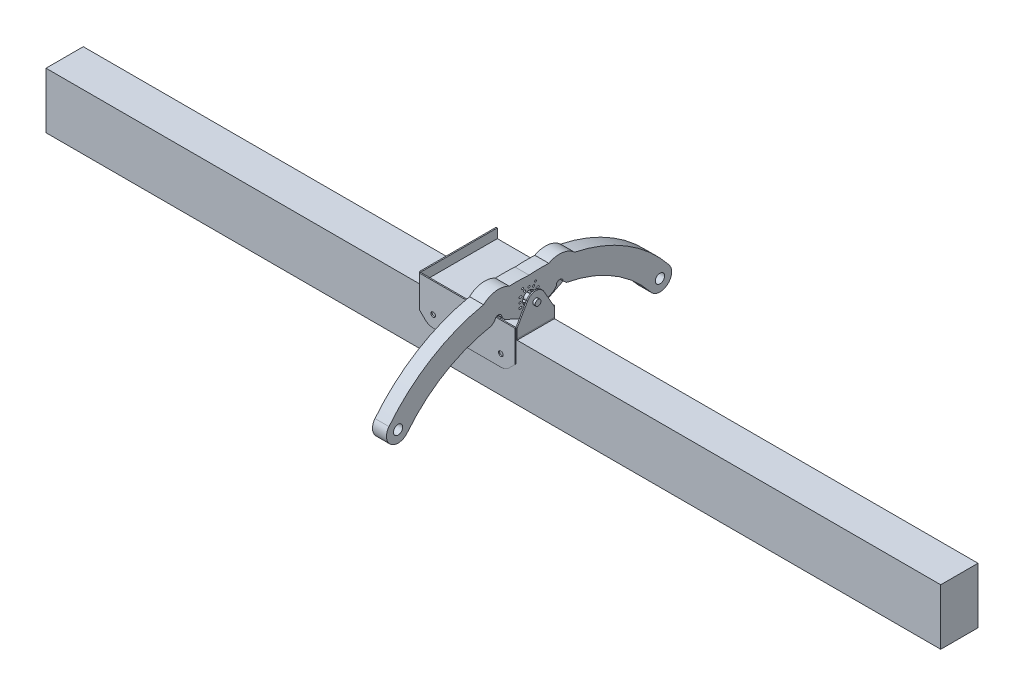
SolidWorks part; units mm, degrees
ref_plane "Front Plane" through (0, 0, 0) normal (0, 0, 1) x (1, 0, 0)
ref_plane "Top Plane" through (0, 0, 0) normal (0, 1, 0) x (1, 0, 0)
ref_plane "Right Plane" through (0, 0, 0) normal (1, 0, 0) x (0, 0, -1)
other "Bounding Box"
ref_plane "Default Plane" through (-8.9266, -12.7485, 0) normal (-0.1736, 0.9848, 0) x (0.9848, 0.1736, 0)
sketch "Sketch1" plane through (0, 0, 0) normal (1, 0, 0) x (0, 0, -1)
  line L0 (26.4895, 47.7116) -> (97.9745, 8.0232)
  line L1 (22.4975, -49.7187) -> (96.9898, -16.0113)
  line L2 (0, 0) -> (91.44, -3.7465) construction
  line L3 (0, -149.6129) -> (0, 49850.3871) construction
  line L4 (62.94, 24.7535) -> (119.94, 24.7535)
  line L5 (62.94, 24.7535) -> (62.94, -32.2465)
  line L6 (62.94, -32.2465) -> (119.94, -32.2465)
  line L7 (119.94, 24.7535) -> (119.94, -32.2465)
  line L8 (62.94, 24.7535) -> (119.94, -32.2465) construction
  line L9 (62.94, -32.2465) -> (119.94, 24.7535) construction
  line L10 (-50.8, -218.44) -> (50.8, -218.44)
  line L11 (-50.8, -218.44) -> (-50.8, -66.04)
  line L12 (-50.8, -66.04) -> (50.8, -66.04)
  line L13 (50.8, -218.44) -> (50.8, -66.04)
  line L14 (-50.8, -218.44) -> (50.8, -66.04) construction
  line L15 (-50.8, -66.04) -> (50.8, -218.44) construction
  line L16 (40.64, -3.7465) -> (40.64, -58.1025)
  line L17 (40.64, -58.1025) -> (142.24, -58.1025)
  line L18 (142.24, -58.1025) -> (142.24, -3.7465)
  line L19 (-33.0655, -62.865) -> (49966.9345, -62.865) construction
  line L20 (-356.8721, -133.429) -> (0, 0) construction
  line L21 (0, 0) -> (356.8721, -133.429) construction
  line L22 (-356.8721, -133.429) -> (356.8721, -133.429) construction
  arc A0 (26.4895, 47.7116) -> (22.4975, -49.7187) centre (0, 0) ccw
  arc A1 (96.9898, -16.0113) -> (97.9745, 8.0232) centre (91.44, -3.7465) ccw
  circle A2 centre (91.44, -3.7465) radius 50.8
  circle A3 centre (0, 0) radius 58.6105 construction
  circle A4 centre (0, 0) radius 7.9375
  circle A5 centre (0, 0) radius 17.4625
  point P13 (0, -142.24)
  point P29 (58.6105, 0)
  point P31 (7.9375, 0)
  point P32 (17.4625, 0)
  point P33 (0, -66.04)
  point P34 (0, -62.865)
  line B0 (-25.4, 10.2108) -> (-21.997, 10.2108)
  line B1 (-10.3326, -22.766) -> (-9.8529, -21.2892)
  line B2 (-13.5106, -19.1774) -> (-14.5497, -20.3313)
  line B3 (24.8822, 2.4348) -> (23.3634, 2.1118)
  line B4 (23.3634, -2.1118) -> (24.8822, -2.4348)
  line B5 (21.997, -15.1892) -> (25.4, -15.1892)
  line B6 (25.4, -10.2108) -> (21.997, -10.2108)
  line B7 (14.5497, -20.3313) -> (13.5106, -19.1774)
  line B8 (9.8529, -21.2892) -> (10.3326, -22.766)
  circle B9 centre (0, 0) radius 57.2931
  arc B10 (2.4892, 25.4) -> (-2.4892, 25.4) centre (0, 25.4) ccw
  arc B11 (19.9517, 30.1625) -> (14.9733, 30.1625) centre (17.4625, 30.1625) ccw
  arc B12 (-21.997, 10.2108) -> (-19.5078, 12.7) centre (-21.997, 12.7) ccw
  arc B13 (-14.9733, -30.1625) -> (-19.9517, -30.1625) centre (-17.4625, -30.1625) ccw
  arc B14 (-19.9517, -30.1625) -> (-14.9733, -30.1625) centre (-17.4625, -30.1625) ccw
  arc B15 (-14.9733, 30.1625) -> (-19.9517, 30.1625) centre (-17.4625, 30.1625) ccw
  arc B16 (2.0452, 14.1404) -> (-2.0452, 14.1404) centre (0, 0) ccw
  arc B17 (2.0452, 14.1404) -> (3.667, 14.6219) centre (2.3342, 16.1389) ccw
  arc B18 (13.2685, 5.299) -> (11.2233, 8.8414) centre (0, 0) ccw
  arc B19 (14.4964, -4.1352) -> (14.4964, 4.1352) centre (13.0969, 0) ccw
  arc B20 (11.2233, -8.8414) -> (13.2685, -5.299) centre (0, 0) ccw
  arc B21 (3.667, -14.6219) -> (10.8294, -10.4867) centre (6.5484, -11.3422) ccw
  arc B22 (-2.0452, -14.1404) -> (-3.667, -14.6219) centre (-2.3342, -16.1389) ccw
  arc B23 (-10.8294, -10.4867) -> (-11.2233, -8.8414) centre (-12.8096, -10.0909) ccw
  arc B24 (-11.2233, 8.8414) -> (-13.2685, 5.299) centre (0, 0) ccw
  arc B25 (-3.667, 14.6219) -> (-10.9141, 11.3422) centre (-6.5484, 11.3422) ccw
  arc B26 (-14.5497, -20.3313) -> (-10.3326, -22.766) centre (-12.7, -21.997) ccw
  arc B27 (-24.8822, 2.4348) -> (-24.8822, -2.4348) centre (-25.4, 0) ccw
  arc B28 (-10.3326, 22.766) -> (-14.5497, 20.3313) centre (-12.7, 21.997) ccw
  arc B29 (14.9733, -30.1625) -> (19.9517, -30.1625) centre (17.4625, -30.1625) ccw
  arc B30 (19.9517, -30.1625) -> (14.9733, -30.1625) centre (17.4625, -30.1625) ccw
  arc B31 (27.8892, 0) -> (24.8822, 2.4348) centre (25.4, 0) ccw
  arc B32 (24.8822, -2.4348) -> (27.8892, 0) centre (25.4, 0) ccw
  arc B33 (23.3634, 2.1118) -> (23.3634, -2.1118) centre (23.8125, 0) ccw
  arc B34 (21.997, 15.1892) -> (21.997, 10.2108) centre (21.997, 12.7) ccw
  arc B35 (27.8892, -12.7) -> (25.4, -10.2108) centre (25.4, -12.7) ccw
  arc B36 (25.4, -15.1892) -> (27.8892, -12.7) centre (25.4, -12.7) ccw
  arc B37 (21.997, -10.2108) -> (21.997, -15.1892) centre (21.997, -12.7) ccw
  arc B38 (15.1892, -21.997) -> (14.5497, -20.3313) centre (12.7, -21.997) ccw
  arc B39 (10.3326, -22.766) -> (15.1892, -21.997) centre (12.7, -21.997) ccw
  arc B40 (13.5106, -19.1774) -> (9.8529, -21.2892) centre (11.9063, -20.6222) ccw
  arc B41 (9.8529, 21.2892) -> (13.5106, 19.1774) centre (11.9062, 20.6222) ccw
  arc B42 (-2.4892, -25.4) -> (2.4892, -25.4) centre (0, -25.4) ccw
  arc B43 (2.4892, -25.4) -> (-2.4892, -25.4) centre (0, -25.4) ccw
  dimension "D1" = 13.462
  dimension "D2" = 117.221
  dimension "D4" = 101.6
  dimension "D11" = 54.5719
  dimension "D13" = 15.875
  dimension "D14" = 34.925
  dimension "D3" = 57
  dimension "D5" = 152.4
  dimension "D6" = 101.6
  dimension "D7" = 66.04
  dimension "D8" = 54.356
  dimension "D9" = 3.175
  dimension "D10" = 4.7625
  dimension "D12" = 91.44
  dimension "D15" = 139
  dimension "D16" = 381
sketch_block_instance "Block-WCP 36T Sprocket Block-1"
sketch_block "Block-WCP 36T Sprocket Block"
sketch "Sketch2" plane through (0, 0, 0) normal (0, 1, 0) x (1, 0, 0)
  line L0 (-185.2438, 91.44) -> (49814.7562, 91.44) construction
  line L1 (-1.9939, 58.6105) -> (1.9939, 58.6105)
  line L2 (-1.9939, 58.6105) -> (-1.9939, -58.6105)
  line L3 (-1.9939, -58.6105) -> (1.9939, -58.6105)
  line L4 (1.9939, 58.6105) -> (1.9939, -58.6105)
  line L5 (-1.9939, 58.6105) -> (1.9939, -58.6105) construction
  line L6 (-1.9939, -58.6105) -> (1.9939, 58.6105) construction
  line L7 (-88.9, 119.94) -> (-17.78, 119.94)
  line L8 (-88.9, 119.94) -> (-88.9, 62.94)
  line L9 (-88.9, 62.94) -> (-17.78, 62.94)
  line L10 (-17.78, 119.94) -> (-17.78, 62.94)
  line L11 (-88.9, 119.94) -> (-17.78, 62.94) construction
  line L12 (-88.9, 62.94) -> (-17.78, 119.94) construction
  line L13 (-180.975, 142.24) -> (-92.075, 142.24)
  line L14 (-180.975, 142.24) -> (-180.975, 40.64)
  line L15 (-180.975, 40.64) -> (-92.075, 40.64)
  line L16 (-92.075, 142.24) -> (-92.075, 40.64)
  line L17 (-180.975, 142.24) -> (-92.075, 40.64) construction
  line L18 (-180.975, 40.64) -> (-92.075, 142.24) construction
  line L19 (0, -356.8721) -> (0, 356.8721) construction
  line L20 (0, 0) -> (50000, 0) construction
  line L21 (-17.78, 62.94) -> (-17.78, -49937.06) construction
  line L22 (71.12, 7.9375) -> (-24.13, 7.9375)
  line L23 (71.12, 7.9375) -> (71.12, -7.9375)
  line L24 (71.12, -7.9375) -> (-24.13, -7.9375)
  line L25 (-24.13, 7.9375) -> (-24.13, -7.9375)
  line L26 (71.12, 7.9375) -> (-24.13, -7.9375) construction
  line L27 (71.12, -7.9375) -> (-24.13, 7.9375) construction
  line L28 (8.3439, 356.8721) -> (46.4439, 356.8721)
  line L29 (8.3439, 356.8721) -> (8.3439, -356.8721)
  line L30 (8.3439, -356.8721) -> (46.4439, -356.8721)
  line L31 (46.4439, 356.8721) -> (46.4439, -356.8721)
  line L32 (8.3439, 356.8721) -> (46.4439, -356.8721) construction
  line L33 (8.3439, -356.8721) -> (46.4439, 356.8721) construction
  line L34 (-14.605, 51.574) -> (-14.605, -49948.426) construction
  line L35 (61.595, -32.0782) -> (61.595, 49967.9218) construction
  line L36 (-3.4925, 16.6624) -> (-14.605, 16.6624)
  line L37 (-3.4925, 16.6624) -> (-3.4925, -16.6624)
  line L38 (-3.4925, -16.6624) -> (-14.605, -16.6624)
  line L39 (-14.605, 16.6624) -> (-14.605, -16.6624)
  line L40 (-3.4925, 16.6624) -> (-14.605, -16.6624) construction
  line L41 (-3.4925, -16.6624) -> (-14.605, 16.6624) construction
  line L42 (-1.9939, 17.4625) -> (6.7437, 17.4625)
  line L43 (-1.9939, 17.4625) -> (-1.9939, -17.4625)
  line L44 (-1.9939, -17.4625) -> (6.7437, -17.4625)
  line L45 (6.7437, 17.4625) -> (6.7437, -17.4625)
  line L46 (-1.9939, 17.4625) -> (6.7437, -17.4625) construction
  line L47 (-1.9939, -17.4625) -> (6.7437, 17.4625) construction
  line L48 (37.7063, 17.4625) -> (46.4439, 17.4625)
  line L49 (37.7063, 17.4625) -> (37.7063, -17.4625)
  line L50 (37.7063, -17.4625) -> (46.4439, -17.4625)
  line L51 (46.4439, 17.4625) -> (46.4439, -17.4625)
  line L52 (37.7063, 17.4625) -> (46.4439, -17.4625) construction
  line L53 (37.7063, -17.4625) -> (46.4439, 17.4625) construction
  line L58 (-68.8345, 50.8) -> (49931.1655, 50.8)
  line L59 (-72.6975, -50.8) -> (49927.3025, -50.8)
  line L60 (64.77, 18.8635) -> (64.77, -49981.1365) construction
  line L62 (50.4825, 16.6624) -> (61.595, 16.6624)
  line L63 (50.4825, 16.6624) -> (50.4825, -16.6624)
  line L64 (50.4825, -16.6624) -> (61.595, -16.6624)
  line L65 (61.595, 16.6624) -> (61.595, -16.6624)
  line L66 (50.4825, 16.6624) -> (61.595, -16.6624) construction
  line L67 (50.4825, -16.6624) -> (61.595, 16.6624) construction
  point P0 (0, 0)
  point P6 (-53.34, 91.44)
  point P12 (-136.525, 91.44)
  point P19 (23.495, 0)
  point P31 (27.3939, 0)
  point P42 (-9.0487, 0)
  point P47 (2.3749, 0)
  point P52 (42.0751, 0)
  point P65 (56.0388, 0)
  point P71 (64.77, 0)
  point P72 (61.595, 0)
  point P73 (-17.78, 0)
  point P74 (64.77, -50.8)
  dimension "D1" = 3.9878
  dimension "D2" = 3.175
  dimension "D3" = 71.12
  dimension "D4" = 88.9
  dimension "D5" = 17.78
  dimension "D6" = 38.1
  dimension "D7" = 6.35
  dimension "D8" = 3.175
  dimension "D9" = 33.3248
  dimension "D10" = 11.1125
  dimension "D11" = 6.35
  dimension "D12" = 8.7376
  dimension "D13" = 76.2
  dimension "D14" = 3.175
  dimension "D15" = 6.35
sketch "Sketch3" plane through (0, 0, 0) normal (1, 0, 0) x (0, 0, -1)
  line L0 (-50.8, -218.44) -> (50.8, -218.44)
  line L1 (50.8, -218.44) -> (50.8, -66.04)
  line L2 (50.8, -66.04) -> (-50.8, -66.04)
  line L3 (-50.8, -66.04) -> (-50.8, -218.44)
extrude "Boss-Extrude1" add sketch "Sketch3" along normal mid plane 2438.4
sketch "Sketch11" plane through (0, -66.04, 0) normal (0, 1, 0) x (1, 0, 0)
  line L0 (-198.755, -50.8) -> (64.77, -50.8)
  line L1 (64.77, -50.8) -> (64.77, 50.8)
  line L2 (-200068.8345, 50.8) -> (249931.1655, 50.8) construction
  line L4 (-14.605, 200051.574) -> (-14.605, -249948.426) construction
  line L5 (-17.78, 158.75) -> (-198.755, 158.75)
  line L6 (-198.755, 158.75) -> (-198.755, -50.8)
  line L7 (64.77, 200018.8635) -> (64.77, -249981.1365) construction
  line L8 (-200072.6975, -50.8) -> (249927.3025, -50.8) construction
  line L9 (-17.78, 200062.94) -> (-17.78, -249937.06) construction
  line L10 (-17.78, 158.75) -> (-17.78, 50.8)
  line L11 (-17.78, 50.8) -> (64.77, 50.8)
  dimension "D1" = 184.15
  dimension "D2" = 107.95
extrude "Boss-Extrude5" add sketch "Sketch11" along normal up to vertex (3.175 mm away) separate body up to point (0, -62.865, 0)
sketch "Sketch12" plane through (0, 0, 0) normal (1, 0, 0) x (0, 0, -1)
  line L0 (-50.8, -62.865) -> (50.8, -62.865)
  line L3 (-50.8, -62.865) -> (-50.8, -37.465)
  line L4 (-50.8, -37.465) -> (-22.0274, 12.6473)
  line L5 (50.8, -62.865) -> (50.8, -37.465)
  line L6 (50.8, -37.465) -> (22.0274, 12.6473)
  line L7 (-50.8, -62.865) -> (50.8, -62.865) construction
  arc A0 (-22.0274, 12.6473) -> (22.0274, 12.6473) centre (0, 0) cw
  circle A1 centre (0, 0) radius 7.9375 construction
  circle A2 centre (0, 0) radius 7.9375
  dimension "D2" = 25.4
  dimension "D1" = 25.4
extrude "Boss-Extrude6" add sketch "Sketch12" along normal up to vertex (64.77 mm away) from vertex separate body up to point (64.77, 0, 50.8) starting at point (61.595, 0, 16.6624)
sketch "Sketch13" plane through (0, 0, 50.8) normal (0, 0, 1) x (1, 0, 0)
  line L0 (-198.755, -66.04) -> (-198.755, -123.6413)
  line L1 (-198.755, -123.6413) -> (-183.1056, -139.2906)
  line L2 (61.595, -66.04) -> (61.595, -123.6413)
  line L3 (61.595, -123.6413) -> (45.9456, -139.2906)
  line L4 (-160.655, -148.59) -> (23.495, -148.59)
  line L5 (-160.655, -116.84) -> (-68.58, -116.84) construction
  line L6 (-68.58, -116.84) -> (23.495, -116.84) construction
  line L7 (1219.2, -66.04) -> (-1219.2, -66.04) construction
  line L8 (-198.755, -66.04) -> (61.595, -66.04)
  line L9 (61.595, -37.465) -> (61.595, -62.865) construction
  line L11 (-198.755, -62.865) -> (-198.755, -66.04) construction
  arc A0 (-183.1056, -139.2906) -> (-160.655, -148.59) centre (-160.655, -116.84) ccw
  arc A1 (45.9456, -139.2906) -> (23.495, -148.59) centre (23.495, -116.84) cw
  circle A2 centre (-160.655, -116.84) radius 6.35
  circle A3 centre (23.495, -116.84) radius 6.35
  circle A4 centre (-68.58, -116.84) radius 6.35
  point P18 (64.77, -66.04)
  point P19 (64.77, -66.04)
  point P24 (-194.0557, -66.04)
  dimension "D1" = 12.7
  dimension "D3" = 31.75
  dimension "D2" = 38.1
  dimension "D4" = 50.8
  dimension "D5" = 45
extrude "Boss-Extrude7" add sketch "Sketch13" along normal blind 3.175 separate body
extrude "Boss-Extrude8" add sketch "Sketch13<2>" against normal blind 3.175 from vertex separate body starting at point (0, -218.44, -50.8)
sketch "Sketch13<2>" plane through (0, 0, 50.8) normal (0, 0, 1) x (1, 0, 0) same geometry as "Sketch13"
sketch "Sketch14" plane through (0, 0, 0) normal (1, 0, 0) x (0, 0, -1)
  line L0 (-50.8, -62.865) -> (158.75, -62.865)
  line L1 (-200033.0655, -62.865) -> (249966.9345, -62.865) construction
  line L2 (158.75, -62.865) -> (158.75, -37.465)
  line L3 (158.75, -37.465) -> (119.3185, -7.0377)
  line L4 (-50.8, -62.865) -> (-50.8, -37.465)
  line L5 (-50.8, -37.465) -> (-21.997, 12.7)
  line L6 (11.2488, 22.7733) -> (70.253, -6.3717)
  line L8 (67.4408, -12.065) -> (115.4392, -12.065) construction
  arc A0 (-21.997, 12.7) -> (11.2488, 22.7733) centre (0, 0) cw
  arc A1 (73.4406, -9.9854) -> (109.4394, -9.9854) centre (91.44, -3.7465) ccw
  arc A2 (119.3185, -7.0377) -> (109.4394, -9.9854) centre (115.4392, -12.065) ccw
  arc A3 (70.253, -6.3717) -> (73.4406, -9.9854) centre (67.4408, -12.065) cw
  circle A4 centre (0, 0) radius 7.9375 construction
  circle A5 centre (0, 0) radius 7.9375
  point P23 (161.1346, -62.865)
  point P24 (158.75, -62.865)
  point P25 (158.75, -62.865)
  point P29 (115.4392, -5.715)
  dimension "D1" = 19.05
  dimension "D4" = 6.35
  dimension "D3" = 57.15
extrude "Boss-Extrude9" add sketch "Sketch14" along normal up to vertex (-14.605 mm away) from vertex separate body up to point (-14.605, 0, -16.6624) starting at point (-17.78, 0, 0)
sketch "Sketch4" plane through (0, 0, 0) normal (1, 0, 0) x (0, 0, -1)
  line L0 (0, -44.45) -> (0, 53.0661)
  line L2 (-102.3094, -15.3884) -> (-82.8518, 0.9384)
  line L3 (-82.8518, 0.9384) -> (-66.525, -18.5191)
  line L4 (0, -200149.6129) -> (0, 249850.3871) construction
  line L6 (-66.525, -18.5191) -> (-18.4414, -40.444)
  line L7 (-53.975, -88.265) -> (-53.975, -62.865) construction
  line L9 (-53.975, -62.865) -> (-28.575, -62.865) construction
  line L11 (-66.525, -18.5191) -> (0, 0) construction
  line L12 (0, 0) -> (-28.575, -62.865) construction
  line L13 (-102.3094, -15.3884) -> (-66.525, -18.5191) construction
  line L14 (-53.975, -88.265) -> (-28.575, -62.865) construction
  line L15 (-53.975, -88.265) -> (0, 0) construction
  line L16 (0, 0) -> (-102.3094, -15.3884) construction
  line L17 (-53.975, -123.6413) -> (-53.975, -66.04) construction
  line L18 (-200033.0655, -62.865) -> (249966.9345, -62.865) construction
  circle A0 centre (-356.8721, -133.429) radius 12.7
  arc A2 (-332.0111, -153.1773) -> (-381.7331, -113.6808) centre (-356.8721, -133.429) cw
  arc A3 (-18.4414, -40.444) -> (0, -44.45) centre (0, 0) ccw
  arc A4 (-332.0111, -153.1773) -> (-102.3094, -15.3884) centre (-33.6791, -390.1562) cw
  arc A5 (-381.7331, -113.6808) -> (-123.9731, 45.0762) centre (-33.6791, -390.1562) cw
  arc A6 (-53.9367, 53.882) -> (0, 53.0661) centre (-33.6791, -390.1562) cw
  arc A7 (-123.9731, 45.0762) -> (-53.9367, 53.882) centre (-82.8518, 0.9384) cw
  point P19 (-57.0317, -60.6593)
  point P25 (-54.1049, 49.2027)
  point P26 (-66.3818, 49.8029)
  dimension "D1" = 19.05
  dimension "D2" = 25.4
  dimension "D3" = 44.45
  dimension "D7" = 381
  dimension "D8" = 60.325
  dimension "D4" = 25.4
  dimension "D5" = 25.4
  dimension "D6" = 50
extrude "Boss-Extrude2" add sketch "Sketch4" along normal up to vertex (46.4439 mm away) from vertex separate body up to point (46.4439, 0, 356.8721) starting at point (8.3439, 0, 356.8721)
sketch "Sketch5" plane through (46.4439, 0, 0) normal (1, 0, 0) x (0, 0, -1)
  line L0 (-88.0113, -3.3909) -> (-83.682, -8.5503) construction
  line L1 (-102.3094, -15.3884) -> (-82.8518, 0.9384) construction
  line L2 (-83.682, -8.5503) -> (-78.5225, -4.2211) construction
  line L3 (-82.8518, 0.9384) -> (-66.525, -18.5191) construction
  circle A0 centre (-83.682, -8.5503) radius 9.525
  dimension "D1" = 19.05
extrude "Cut-Extrude1" cut sketch "Sketch5" against normal through all
mirror "Mirror1" about plane through (0, 0, 0) normal (0, 0, 1) of bodies 106
sketch "Sketch6" plane through (8.3439, 0, 0) normal (-1, 0, 0) x (0, 0, 1)
  circle A0 centre (0, 0) radius 44.45
  arc A1 (-18.4414, -40.444) -> (18.4414, -40.444) centre (0, 0) ccw construction
extrude "Boss-Extrude3" add sketch "Sketch6" along normal up to vertex (6.35 mm away) separate body up to point (1.9939, 0, 58.6105)
sketch "Sketch7" plane through (1.9939, 0, 0) normal (-1, 0, 0) x (0, 0, 1)
  line L0 (-24.8822, 2.4348) -> (-23.3634, 2.1118) construction
  line L1 (-23.3634, -2.1118) -> (-24.8822, -2.4348) construction
  line L2 (-25.4, -10.2108) -> (-21.997, -10.2108) construction
  line L3 (-21.997, -15.1892) -> (-25.4, -15.1892) construction
  line L4 (-9.8529, -21.2892) -> (-10.3326, -22.766) construction
  line L5 (-14.5497, -20.3313) -> (-13.5106, -19.1774) construction
  line L6 (-24.8822, 2.4348) -> (-23.3634, 2.1118)
  line L7 (-23.3634, -2.1118) -> (-24.8822, -2.4348)
  line L8 (-25.4, -10.2108) -> (-21.997, -10.2108)
  line L9 (-21.997, -15.1892) -> (-25.4, -15.1892)
  line L10 (-9.8529, -21.2892) -> (-10.3326, -22.766)
  line L11 (-14.5497, -20.3313) -> (-13.5106, -19.1774)
  arc A0 (-27.8892, 0) -> (-24.8822, -2.4348) centre (-25.4, 0) ccw construction
  arc A1 (-24.8822, 2.4348) -> (-27.8892, 0) centre (-25.4, 0) ccw construction
  arc A2 (-23.3634, -2.1118) -> (-23.3634, 2.1118) centre (-23.8125, 0) ccw construction
  arc A3 (-25.4, -10.2108) -> (-27.8892, -12.7) centre (-25.4, -12.7) ccw construction
  arc A4 (-27.8892, -12.7) -> (-25.4, -15.1892) centre (-25.4, -12.7) ccw construction
  arc A5 (-21.997, -15.1892) -> (-21.997, -10.2108) centre (-21.997, -12.7) ccw construction
  arc A6 (-2.4892, -25.4) -> (2.4892, -25.4) centre (0, -25.4) ccw construction
  arc A7 (2.4892, -25.4) -> (-2.4892, -25.4) centre (0, -25.4) ccw construction
  arc A8 (-9.8529, -21.2892) -> (-13.5106, -19.1774) centre (-11.9063, -20.6222) ccw construction
  arc A9 (-14.5497, -20.3313) -> (-15.1892, -21.997) centre (-12.7, -21.997) ccw construction
  arc A10 (-15.1892, -21.997) -> (-10.3326, -22.766) centre (-12.7, -21.997) ccw construction
  arc A11 (-14.9733, -30.1625) -> (-19.9517, -30.1625) centre (-17.4625, -30.1625) ccw construction
  arc A12 (-19.9517, -30.1625) -> (-14.9733, -30.1625) centre (-17.4625, -30.1625) ccw construction
  arc A13 (-27.8892, 0) -> (-24.8822, -2.4348) centre (-25.4, 0) ccw
  arc A14 (-24.8822, 2.4348) -> (-27.8892, 0) centre (-25.4, 0) ccw
  arc A15 (-23.3634, -2.1118) -> (-23.3634, 2.1118) centre (-23.8125, 0) ccw
  arc A16 (-25.4, -10.2108) -> (-27.8892, -12.7) centre (-25.4, -12.7) ccw
  arc A17 (-27.8892, -12.7) -> (-25.4, -15.1892) centre (-25.4, -12.7) ccw
  arc A18 (-21.997, -15.1892) -> (-21.997, -10.2108) centre (-21.997, -12.7) ccw
  arc A19 (-2.4892, -25.4) -> (2.4892, -25.4) centre (0, -25.4) ccw
  arc A20 (2.4892, -25.4) -> (-2.4892, -25.4) centre (0, -25.4) ccw
  arc A21 (-9.8529, -21.2892) -> (-13.5106, -19.1774) centre (-11.9063, -20.6222) ccw
  arc A22 (-14.5497, -20.3313) -> (-15.1892, -21.997) centre (-12.7, -21.997) ccw
  arc A23 (-15.1892, -21.997) -> (-10.3326, -22.766) centre (-12.7, -21.997) ccw
  arc A24 (-14.9733, -30.1625) -> (-19.9517, -30.1625) centre (-17.4625, -30.1625) ccw
  arc A25 (-19.9517, -30.1625) -> (-14.9733, -30.1625) centre (-17.4625, -30.1625) ccw
  circle A27 centre (0, 0) radius 14.2875
  dimension "D1" = 28.575
extrude "Cut-Extrude2" cut sketch "Sketch7" against normal through all
mirror "Mirror2" about plane through (0, 0, 0) normal (0, 0, 1) of "Cut-Extrude2" second plane through (0, 0, 0) second plane normal (0, 1, 0)
sketch "Sketch8" plane through (1.9939, 0, 0) normal (-1, 0, 0) x (0, 0, 1)
  circle A0 centre (0, 0) radius 17.4625
  circle A1 centre (0, 0) radius 17.4625 construction
extrude "Cut-Extrude3" cut sketch "Sketch8" against normal up to vertex (4.7498 mm away) up to point (6.7437, 0, 17.4625)
sketch "Sketch9" plane through (46.4439, 0, 0) normal (1, 0, 0) x (0, 0, -1)
  circle A0 centre (0, 0) radius 17.4625 construction
  circle A1 centre (0, 0) radius 17.4625
extrude "Cut-Extrude4" cut sketch "Sketch9" against normal up to vertex (8.7376 mm away) up to point (37.7063, 0, 17.4625)
sketch "Sketch10" plane through (0, 0, 0) normal (1, 0, 0) x (0, 0, -1)
  circle A0 centre (0, 0) radius 7.9375 construction
  circle A1 centre (0, 0) radius 7.9375
extrude "Boss-Extrude4" add sketch "Sketch10" along normal up to vertex (71.12 mm away) and the other way up to vertex (24.13 mm away) separate body up to point (71.12, 0, 7.9375) other way up to point (-24.13, 0, 7.9375)
sketch "Sketch15" plane through (0, 0, 53.975) normal (0, 0, 1) x (1, 0, 0)
  line L0 (61.595, 12.6473) -> (61.595, -37.465) construction
  line L1 (-198.755, -66.04) -> (61.595, -66.04)
  line L2 (-198.755, -66.04) -> (-198.755, -37.465)
  line L3 (-198.755, -37.465) -> (61.595, -37.465)
  line L4 (61.595, -66.04) -> (61.595, -37.465)
  line L5 (-198.755, -66.04) -> (61.595, -37.465) construction
  line L6 (-198.755, -37.465) -> (61.595, -66.04) construction
  line L7 (61.595, -37.465) -> (61.595, -62.865) construction
  line L8 (64.77, -37.465) -> (61.595, -37.465) construction
  point P4 (-68.58, -51.7525)
  point P7 (61.595, -37.465)
  point P10 (61.595, -37.465)
  point P13 (61.595, -37.465)
extrude "Boss-Extrude11" add sketch "Sketch15" against normal up to surface (3.175 mm away) up to face at (-66.9925, -64.4525, 50.8)
sketch "Sketch16" plane through (-14.605, 0, 0) normal (1, 0, 0) x (0, 0, -1)
  line L0 (53.975, -62.865) -> (53.975, -113.665)
  line L1 (-200033.0655, -62.865) -> (249966.9345, -62.865) construction
  line L2 (53.975, -123.6413) -> (53.975, -66.04) construction
  line L4 (158.75, -66.04) -> (158.75, -62.865)
  line L5 (158.75, -62.865) -> (53.975, -62.865)
  line L6 (53.975, -113.665) -> (63.5, -113.665)
  line L7 (63.5, -113.665) -> (158.75, -66.04)
  dimension "D1" = 9.525
  dimension "D2" = 50.8
extrude "Boss-Extrude12" add sketch "Sketch16" against normal up to surface (3.175 mm away) up to face at (-17.78, -64.4525, -104.775)
sketch "Sketch17" plane through (0, 0, -50.8) normal (0, 0, -1) x (-1, 0, 0)
  line L0 (-61.595, -66.04) -> (17.78, -66.04)
  line L1 (-1219.2, -66.04) -> (1219.2, -66.04) construction
  line L2 (17.78, -66.04) -> (17.78, -62.865)
  line L3 (17.78, -62.865) -> (14.605, -62.865)
  line L4 (-64.77, -62.865) -> (17.78, -62.865) construction
  line L5 (14.605, -62.865) -> (14.605, -37.465)
  line L6 (14.605, -37.465) -> (11.43, -37.465)
  line L7 (11.43, -37.465) -> (2.6289, -62.865)
  line L8 (2.6289, -62.865) -> (-49.6189, -62.865)
  line L9 (-49.6189, -62.865) -> (-58.42, -37.465)
  line L10 (-58.42, -37.465) -> (-61.595, -37.465)
  line L11 (-61.595, -37.465) -> (-61.595, -66.04)
  line L12 (17.78, -62.865) -> (17.78, -66.04) construction
  line L15 (14.605, -62.865) -> (14.605, -113.665) construction
  line L16 (-61.595, -66.04) -> (198.755, -66.04) construction
  line L18 (-61.595, -62.865) -> (-61.595, -37.465) construction
  line L19 (-46.4439, -18.5191) -> (-46.4439, -40.444) construction
  point P18 (0, 0)
  point P19 (-49.333, -62.865)
  dimension "D1" = 3.175
  dimension "D2" = 3.175
extrude "Boss-Extrude13" add sketch "Sketch17" along normal up to surface (3.175 mm away) up to face at (-62.23, -116.84, -53.975)
sketch "Sketch18" plane through (-198.755, 0, 0) normal (-1, 0, 0) x (0, 0, 1)
  line L0 (-158.75, -66.04) -> (-63.5, -113.665)
  line L1 (-63.5, -113.665) -> (-50.8, -113.665)
  line L2 (-50.8, -113.665) -> (-50.8, -66.04)
  line L3 (-158.75, -66.04) -> (50.8, -66.04) construction
  line L4 (-50.8, -66.04) -> (50.8, -66.04)
  line L5 (50.8, -66.04) -> (50.8, -37.465)
  line L6 (50.8, -37.465) -> (-158.75, -37.465)
  line L7 (-158.75, -37.465) -> (-158.75, -66.04)
  line L8 (50.8, -37.465) -> (53.975, -37.465) construction
  line L10 (-50.8, -66.04) -> (-50.8, -123.6413) construction
  point P4 (50.8, -40.1726)
  point P16 (-61.5414, -66.04)
extrude "Boss-Extrude14" add sketch "Sketch18" along normal blind 3.175 separate body
